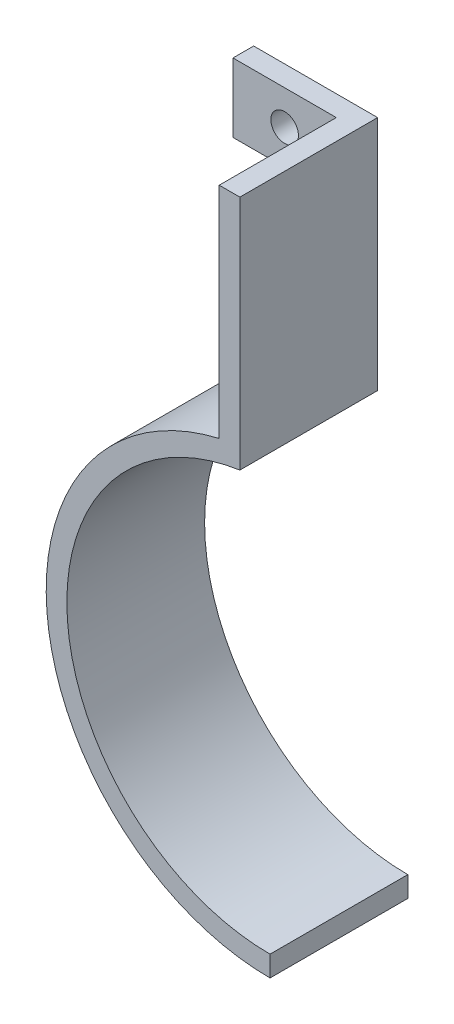
SolidWorks part; units mm, degrees
ref_plane "Front Plane" through (0, 0, 0) normal (0, 0, 1) x (1, 0, 0)
ref_plane "Top Plane" through (0, 0, 0) normal (0, 1, 0) x (1, 0, 0)
ref_plane "Right Plane" through (0, 0, 0) normal (1, 0, 0) x (0, 0, -1)
sketch "Sketch1" plane through (0, 0, 0) normal (0, 0, 1) x (1, 0, 0)
  line L1 (0, -29.5) -> (0, -32.5)
  line L2 (-4.3787, 29.1732) -> (-4.3787, 32.2037)
  arc A0 (-4.3787, 32.2037) -> (0, -32.5) centre (0, 0) ccw
  arc A1 (-4.3787, 29.1732) -> (0, -29.5) centre (0, 0) ccw
  dimension "D1" = 65
extrude "Boss-Extrude1" add sketch "Sketch1" along normal blind 20
ref_axis "Axis1" through (0, 0, 20) along (0, 0, -1)
ref_plane "Plane2" through (0, 0, 0) normal (0, -1, 0) x (0, 0, -1)
ref_plane "Plane3" through (0, 32.5, 0) normal (0, 1, 0) x (1, 0, 0)
sketch "Sketch3" plane through (0, 32.5, 0) normal (0, 1, 0) x (1, 0, 0)
  line L0 (-4.3787, -20) -> (-4.3787, 0) construction
  line L1 (-4.3787, -20) -> (-4.3787, 0)
  line L2 (-4.3787, 0) -> (-7.3787, 0)
  line L3 (-7.3787, 0) -> (-7.3787, -20)
  line L5 (-7.3787, -20) -> (-4.3787, -20)
  dimension "D1" = 3
  dimension "D2" = 20
extrude "Boss-Extrude3" add sketch "Sketch3" along normal blind 31 and the other way up to surface other way up to face at (-17.3076, -1.1713, 10)
sketch "Sketch4" plane through (-7.3787, 0, 0) normal (-1, 0, 0) x (0, 0, 1)
  line L0 (3, 53.5) -> (3, 63.5)
  line L1 (3, 53.5) -> (0, 53.5)
  line L2 (0, 31.6513) -> (0, 63.5) construction
  line L8 (0, 63.5) -> (0, 53.5)
  line L11 (3, 63.5) -> (0, 63.5)
  dimension "D2" = 3
  dimension "D3" = 10
extrude "Boss-Extrude4" add sketch "Sketch4" along normal blind 15
sketch "Sketch6" plane through (0, 0, 3) normal (0, 0, 1) x (1, 0, 0)
  line L0 (-22.3787, 53.5) -> (-7.3787, 53.5) construction
  line L1 (-22.3787, 53.5) -> (-22.3787, 63.5) construction
  circle A0 centre (-14.8787, 58.5) radius 2
  dimension "D1" = 4
  dimension "D3" = 7.5
  dimension "D2" = 5
extrude "Cut-Extrude2" cut sketch "Sketch6" against normal up to surface (3 mm away) up to face at (-15.5123, 28.4379, 0)
